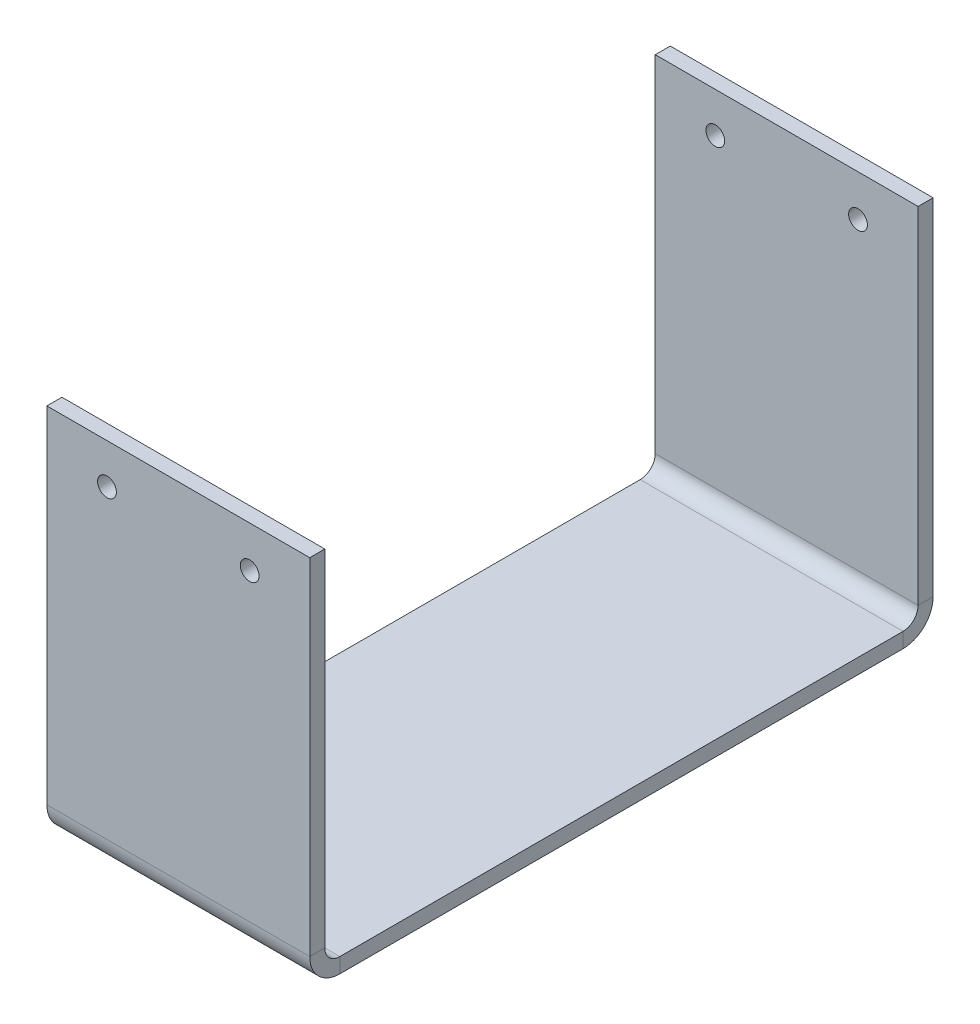
SolidWorks part; units mm, degrees
note: The reader was unsure of these and kept them because the rebuilt part matched: flange length of "Edge-Flange3".
ref_plane "Front Plane" through (0, 0, 0) normal (0, 0, 1) x (1, 0, 0)
ref_plane "Top Plane" through (0, 0, 0) normal (0, 1, 0) x (1, 0, 0)
ref_plane "Right Plane" through (0, 0, 0) normal (1, 0, 0) x (0, 0, -1)
sketch "Sketch1" plane through (0, 0, 0) normal (0, 1, 0) x (1, 0, 0)
  line L1 (-17.5, 41.5) -> (17.5, 41.5)
  line L2 (-17.5, 41.5) -> (-17.5, -41.5)
  line L3 (-17.5, -41.5) -> (17.5, -41.5)
  line L4 (17.5, 41.5) -> (17.5, -41.5)
  line L5 (-17.5, 41.5) -> (17.5, -41.5) construction
  line L6 (-17.5, -41.5) -> (17.5, 41.5) construction
  point P0 (0, 0)
  dimension "D1" = 83
  dimension "D2" = 35
base flange "Base-Flange2" sketch "Sketch1" thickness 2 reverse thickness direction no parameters "D1"=2
edge flange "Edge-Flange3" sketch "Sketch21" flange profiles "Sketch21", "Sketch22" flange angle 90 flange length 50 flange position material inside bend radius 2 thickness 2 relief rectangular parameters "D6"=10, "D8"=1
sketch "Sketch21" plane through (0, 0, -41.5) normal (0, 0, -1) x (-1, 0, 0)
  line L0 (-17.5, 0) -> (17.5, 0) construction
  line L1 (-17.5, 0) -> (17.5, 0)
  line L2 (-17.5, 0) -> (-17.5, 48)
  line L3 (-17.5, 48) -> (17.5, 48)
  line L4 (17.5, 48) -> (17.5, 0)
sketch "Sketch22" plane through (0, 0, 41.5) normal (0, 0, 1) x (1, 0, 0)
  line L0 (-17.5, 0) -> (17.5, 0) construction
  line L1 (-17.5, 0) -> (17.5, 0)
  line L2 (-17.5, 0) -> (-17.5, 48)
  line L3 (-17.5, 48) -> (17.5, 48)
  line L4 (17.5, 48) -> (17.5, 0)
bend "EdgeBend3" bend radius 2 bend angle 90 parameters "D5"=1
bend "EdgeBend4" bend radius 2 bend angle 90 parameters "D5"=2
hole_wizard "Tap Drill for M3 Tap1" positions "Sketch23" profile "Sketch24" hole size "M3" standard "AS" end condition through all
sketch "Sketch23" plane through (-15.8304, -23.0698, -43.5) normal (0, 0, -1) x (-1, 0, 0)
  point P0 (-25.3304, 65.5698)
  point P2 (-6.3304, 65.7399)
sketch "Sketch24" plane through (9.5, 42.5, -43.5) normal (1, 0, 0) x (0, 1, 0)
  line L0 (0, 0) -> (0, 85)
  line L1 (0, 85) -> (1.25, 85)
  line L2 (1.25, 85) -> (1.25, 0)
  line L3 (1.25, 0) -> (0, 0)
  line L4 (0, -6.35) -> (0, 107.95) construction
  dimension "Thru Hole Dia." = 2.5
  dimension "Thru Hole Depth" = 85
sketch "Bend-Lines3" [suppressed] plane through (0, 0, 0) normal (0, 1, 0) x (1, 0, 0)
sketch "Bounding-Box3" [suppressed] plane through (0, 0, 0) normal (0, 1, 0) x (1, 0, 0)
sheet metal parameters "Sheet-Metal3" thickness 2 parameters "D1"=2
flat pattern "Flat-Pattern3" [suppressed]
sketch "Bend-Lines4" plane through (0, 0, 0) normal (0, 1, 0) x (1, 0, 0)
sketch3d "Bounding-Box4" [suppressed]
  line L0 (-20, 40, 0) -> (-20, -40, 0) construction
  line L1 (20, 40, 0) -> (20, -40, 0) construction
  line L2 (-20, 40, 0) -> (20, 40, 0) construction
  line L3 (-20, -40, 0) -> (20, -40, 0) construction
sheet metal parameters "Sheet-Metal5" thickness 2 parameters "D1"=2
flat pattern "Flat-Pattern3"
sketch "Bend-Lines4" plane through (0, 0, 0) normal (0, 1, 0) x (1, 0, 0)
  line L0 (-17.5, -39.8562) -> (17.5, -39.8562) construction
  line L1 (17.5, 39.8562) -> (-17.5, 39.8562) construction
  line L2 (-17.5, -39.8562) -> (17.5, -39.8562) construction
  line L3 (17.5, 39.8562) -> (-17.5, 39.8562) construction
sketch3d "Bounding-Box4" [suppressed]
  line L0 (-17.5, 88.2124, 0) -> (-17.5, -88.2124, 0) construction
  line L1 (17.5, 88.2124, 0) -> (17.5, -88.2124, 0) construction
  line L2 (-17.5, 88.2124, 0) -> (17.5, 88.2124, 0) construction
  line L3 (-17.5, -88.2124, 0) -> (17.5, -88.2124, 0) construction
bend of the flat pattern "Flatten-<EdgeBend3>1"
bend of the flat pattern "Flatten-<EdgeBend4>1"
sheet metal parameters "Sheet-Metal6" thickness 2 parameters "D1"=2
flat pattern "Flat-Pattern3"
sketch "Bend-Lines4" plane through (0, 0, 0) normal (0, 1, 0) x (1, 0, 0)
  line L0 (-17.5, -39.8562) -> (17.5, -39.8562) construction
  line L1 (17.5, 39.8562) -> (-17.5, 39.8562) construction
  line L2 (-17.5, -39.8562) -> (17.5, -39.8562) construction
  line L3 (17.5, 39.8562) -> (-17.5, 39.8562) construction
sketch3d "Bounding-Box4" [suppressed]
  line L0 (-17.5, 88.2124, 0) -> (-17.5, -88.2124, 0) construction
  line L1 (17.5, 88.2124, 0) -> (17.5, -88.2124, 0) construction
  line L2 (-17.5, 88.2124, 0) -> (17.5, 88.2124, 0) construction
  line L3 (-17.5, -88.2124, 0) -> (17.5, -88.2124, 0) construction
bend of the flat pattern "Flatten-<EdgeBend3>1"
bend of the flat pattern "Flatten-<EdgeBend4>1"
